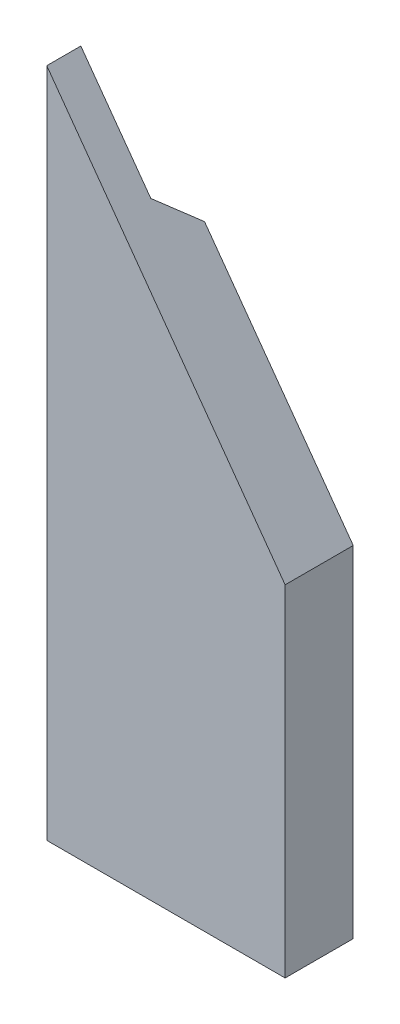
SolidWorks part; units mm, degrees
ref_plane "Front Plane" through (0, 0, 0) normal (0, 0, 1) x (1, 0, 0)
ref_plane "Top Plane" through (0, 0, 0) normal (0, 1, 0) x (1, 0, 0)
ref_plane "Right Plane" through (0, 0, 0) normal (1, 0, 0) x (0, 0, -1)
sketch "Sketch1" plane through (0, 0, 0) normal (0, 1, 0) x (1, 0, 0)
  line L0 (-60, 0) -> (-41.5, 0)
  line L1 (-60, 9) -> (60, 9)
  line L2 (-60, 9) -> (-60, -9)
  line L3 (-60, -9) -> (60, -9)
  line L4 (60, 9) -> (60, -9)
  line L5 (-60, 9) -> (60, -9) construction
  line L6 (-60, -9) -> (60, 9) construction
  line L7 (-41.5, 0) -> (-36.3038, 9)
  line L8 (-41.5, 0) -> (-41.5, 9) construction
  line L9 (60, 0) -> (54.8038, 9)
  line L10 (60, 0) -> (50.5, 0)
  line L11 (50.5, 0) -> (50.5, -9)
  line L13 (0, 9) -> (0, -9) construction
  point P0 (0, 0)
  dimension "D1" = 120
  dimension "D2" = 18
  dimension "D3" = 18.5
  dimension "D4" = 30
  dimension "D5" = 9.5
  dimension "D6" = 30
extrude "Shape" add sketch "Sketch1" along normal blind 800 contours L3 L11 L10 L9 L1 L7 L0 L2 region at (1.7695, 0, 0.3466)
ref_plane "Plane1" [suppressed] through (-60, 790, 9) normal (0.5851, -0.811, 0) x (-0.811, -0.5851, 0)
sketch "Sketch3" [suppressed] plane through (0, 0, 9) normal (0, 0, 1) x (1, 0, 0)
  line L1 (-60, 790) -> (445, 90) construction
  line L3 (-60, 790) -> (445, 90)
  line L6 (50.5, 0) -> (60, 0)
  line L7 (60, 0) -> (60, 800)
  line L8 (60, 800) -> (50.5, 800)
  line L9 (50.5, 800) -> (50.5, 0)
  line L10 (50.5, 0) -> (60, 0)
  line L11 (60, 0) -> (60, 800)
  line L12 (60, 800) -> (50.5, 800)
  line L13 (50.5, 800) -> (50.5, 0)
  dimension "D1" = 0
extrude "Cut-Extrude1" [suppressed] cut sketch "Sketch3" against normal up to next
sketch "Sketch4" [suppressed] plane through (0, 0, 9) normal (0, 0, 1) x (1, 0, 0)
  line L0 (-170.5, 790) -> (334.5, 90) construction
  line L1 (-170.5, 790) -> (334.5, 90)
  line L6 (50.5, 0) -> (60, 0)
  line L7 (60, 0) -> (60, 800)
  line L8 (60, 800) -> (50.5, 800)
  line L9 (50.5, 800) -> (50.5, 0)
  line L10 (50.5, 0) -> (60, 0)
  line L11 (60, 0) -> (60, 800)
  line L12 (60, 800) -> (50.5, 800)
  line L13 (50.5, 800) -> (50.5, 0)
  dimension "D1" = 0
extrude "Cut-Extrude2" [suppressed] cut sketch "Sketch4" against normal through all and the other way through all
sketch "Sketch5" [suppressed] plane through (0, 0, 9) normal (0, 0, 1) x (1, 0, 0)
  line L0 (-281, 790) -> (224, 90) construction
  line L1 (-281, 790) -> (224, 90)
  line L4 (50.5, 0) -> (60, 0)
  line L5 (60, 0) -> (60, 800)
  line L6 (60, 800) -> (50.5, 800)
  line L7 (50.5, 800) -> (50.5, 0)
  line L8 (50.5, 0) -> (60, 0)
  line L9 (60, 0) -> (60, 800)
  line L10 (60, 800) -> (50.5, 800)
  line L11 (50.5, 800) -> (50.5, 0)
  dimension "D1" = 0
extrude "Cut-Extrude3" [suppressed] cut sketch "Sketch5" against normal up to next
sketch "Sketch6" [suppressed] plane through (0, 0, 9) normal (0, 0, 1) x (1, 0, 0)
  line L0 (-391.5, 790) -> (113.5, 90) construction
  line L1 (-391.5, 790) -> (113.5, 90)
  line L6 (50.5, 0) -> (60, 0)
  line L7 (60, 0) -> (60, 800)
  line L8 (60, 800) -> (50.5, 800)
  line L9 (50.5, 800) -> (50.5, 0)
  line L10 (50.5, 0) -> (60, 0)
  line L11 (60, 0) -> (60, 800)
  line L12 (60, 800) -> (50.5, 800)
  line L13 (50.5, 800) -> (50.5, 0)
  dimension "D1" = 0
extrude "Cut-Extrude4" [suppressed] cut sketch "Sketch6" against normal up to next
sketch "Sketch7" plane through (0, 0, 9) normal (0, 0, 1) x (1, 0, 0)
  line L0 (-502, 790) -> (3, 90) construction
  line L1 (-502, 790) -> (3, 90)
  line L2 (3, 90) -> (3, 0)
  line L3 (-60, 0) -> (50.5, 0) construction
  line L8 (50.5, 0) -> (60, 0)
  line L9 (60, 0) -> (60, 800)
  line L10 (60, 800) -> (50.5, 800)
  line L11 (50.5, 800) -> (50.5, 0)
  line L12 (50.5, 0) -> (60, 0)
  line L13 (60, 0) -> (60, 800)
  line L14 (60, 800) -> (50.5, 800)
  line L15 (50.5, 800) -> (50.5, 0)
  line M5 (-60, 0) -> (50.5, 0)
  line M6 (50.5, 0) -> (50.5, 800)
  line M7 (50.5, 800) -> (-60, 800)
  line M8 (-60, 800) -> (-60, 0)
  dimension "D1" = 0
extrude "Cut-Extrude5" cut sketch "Sketch7" against normal up to next contours L1 L2 M5 M6 M7 M8 | L13 L14 L12 M6 region at (-1.8883, 434.8281, 9) region at (55.25, 400, 9)
